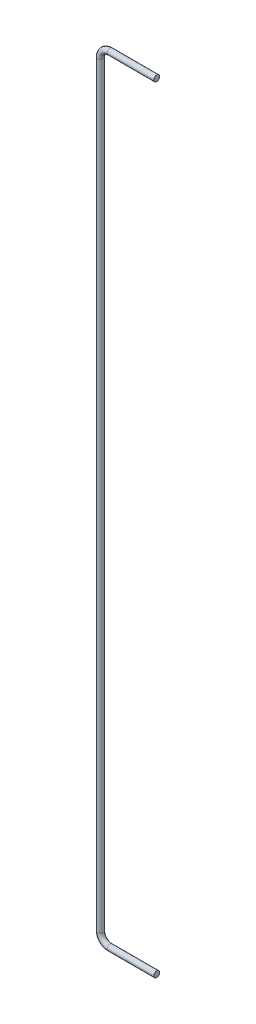
SolidWorks part; units mm, degrees
ref_plane "Plan de face" through (0, 0, 0) normal (0, 0, 1) x (1, 0, 0)
ref_plane "Plan de dessus" through (0, 0, 0) normal (0, 1, 0) x (1, 0, 0)
ref_plane "Plan de droite" through (0, 0, 0) normal (1, 0, 0) x (0, 0, -1)
sketch "Esquisse1" plane through (0, 0, 0) normal (0, 0, 1) x (1, 0, 0)
  line L0 (0, 0) -> (-24, 0)
  line L1 (-29, 5) -> (-29, 395)
  line L2 (-24, 400) -> (0, 400)
  arc A0 (-24, 0) -> (-29, 5) centre (-24, 5) cw
  arc A1 (-29, 395) -> (-24, 400) centre (-24, 395) cw
  dimension "D3" = 5
  dimension "D1" = 24
  dimension "D2" = 400
sketch "Esquisse2" plane through (0, 0, 0) normal (1, 0, 0) x (0, 0, -1)
  circle A0 centre (0, 0) radius 1.5
  dimension "D1" = 3
sweep "Balayage1" add profiles "Esquisse2" path "Esquisse1"
ref_axis "Axe1" through (-24, 400, 0) along (1, 0, 0)
